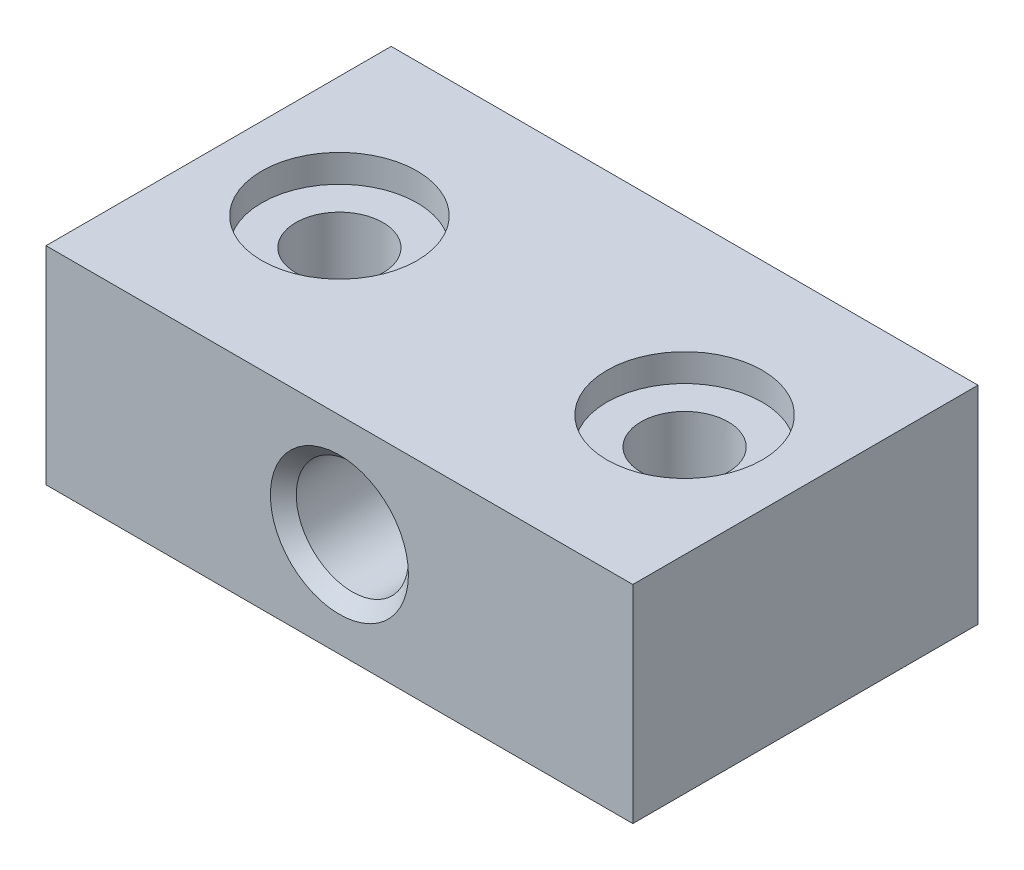
SolidWorks part; units mm, degrees
ref_plane "Front Plane" through (0, 0, 0) normal (0, 0, 1) x (1, 0, 0)
ref_plane "Top Plane" through (0, 0, 0) normal (0, 1, 0) x (1, 0, 0)
ref_plane "Right Plane" through (0, 0, 0) normal (1, 0, 0) x (0, 0, -1)
sketch "Sketch1" plane through (0, 0, 0) normal (0, 0, 1) x (1, 0, 0)
  line L1 (-17, 6) -> (17, 6)
  line L2 (-17, 6) -> (-17, -6)
  line L3 (-17, -6) -> (17, -6)
  line L4 (17, 6) -> (17, -6)
  line L5 (-17, 6) -> (17, -6) construction
  line L6 (-17, -6) -> (17, 6) construction
  point P0 (0, 0)
  dimension "D1" = 34
  dimension "D2" = 12
extrude "Boss-Extrude1" add sketch "Sketch1" against normal blind 20
sketch "Sketch2" plane through (0, 0, 0) normal (0, 0, 1) x (1, 0, 0)
  circle A0 centre (0, 0) radius 3.25
  dimension "D1" = 6.5
extrude "Cut-Extrude1" cut sketch "Sketch2" against normal blind 20 contours A0
sketch "Sketch3" plane through (0, 6, 0) normal (0, 1, 0) x (1, 0, 0)
  line L0 (-17, 20) -> (-17, 0) construction
  line L1 (17, 20) -> (17, 0) construction
  circle A0 centre (-10, 10) radius 2.525
  circle A1 centre (10, 10) radius 2.525
  point P6 (-17, 10)
  point P7 (17, 10)
  dimension "D1" = 5.05
  dimension "D2" = 7
  dimension "D3" = 20
extrude "Cut-Extrude2" cut sketch "Sketch3" against normal blind 20
sketch "Sketch4" plane through (0, 6, 0) normal (0, 1, 0) x (1, 0, 0)
  circle A9 centre (-10, 10) radius 4.5
  circle A10 centre (-10, 10) radius 4.5
  circle A12 centre (10, 10) radius 4.5
  circle A13 centre (10, 10) radius 4.5
  dimension "D1" = 1.975
  dimension "D2" = 1.975
extrude "Cut-Extrude3" cut sketch "Sketch4" against normal blind 1.6
sketch "Sketch5" plane through (0, -6, 0) normal (0, -1, 0) x (1, 0, 0)
  line L1 (10, -5.38) -> (5.999, -7.69)
  line L2 (5.999, -7.69) -> (5.999, -12.31)
  line L3 (5.999, -12.31) -> (10, -14.62)
  line L4 (10, -14.62) -> (14.001, -12.31)
  line L5 (14.001, -12.31) -> (14.001, -7.69)
  line L6 (14.001, -7.69) -> (10, -5.38)
  line L7 (-10, -5.38) -> (-14.001, -7.69)
  line L8 (-14.001, -7.69) -> (-14.001, -12.31)
  line L9 (-14.001, -12.31) -> (-10, -14.62)
  line L10 (-10, -14.62) -> (-5.999, -12.31)
  line L11 (-5.999, -12.31) -> (-5.999, -7.69)
  line L12 (-5.999, -7.69) -> (-10, -5.38)
  circle A0 centre (10, -10) radius 4.001 construction
  circle A1 centre (-10, -10) radius 4.001 construction
  dimension "D1" = 9.24
extrude "Cut-Extrude4" cut sketch "Sketch5" against normal blind 4.97
ref_plane "Plane1" through (0, 0, -22) normal (0, 0, -1) x (-1, 0, 0)
sketch "Sketch6" plane through (0, 0, -22) normal (0, 0, -1) x (-1, 0, 0)
  circle A0 centre (0, 0) radius 3.25 construction
  circle A1 centre (0, 0) radius 3.25
curve "Helix/Spiral1" pitch 8 height 24 turns 3
chamfer "Chamfer1" distance 0.75 angle 45 1 edges at (3.25, 0, -20)
chamfer "Chamfer2" distance 0.75 angle 45 1 edges at (3.25, 0, 0)
sketch "Sketch7" plane through (0, 0, -22) normal (0, 0, -1) x (-1, 0, 0)
  line L0 (3.2839, 0) -> (-3.2161, 0) construction
  line L2 (4.4, 0.9) -> (4.4, -0.9)
  line L3 (-0.8243, 4.3661) -> (0.9757, 4.3661)
  line L4 (0.9757, 4.3661) -> (0.5839, 3.2161)
  line L5 (-0.8243, 4.3661) -> (-0.5161, 3.2161)
  line L6 (-0.5161, 3.2161) -> (-0.5161, -3.2161) construction
  line L7 (0.5839, 3.2161) -> (0.5839, -3.2161) construction
  line L8 (-3.1823, 0.55) -> (3.25, 0.55) construction
  line L9 (-3.1823, -0.55) -> (3.25, -0.55) construction
  line L10 (3.25, 0.55) -> (4.4, 0.9)
  line L11 (3.25, -0.55) -> (4.4, -0.9)
  line L12 (-0.8661, -4.3661) -> (0.9339, -4.3661)
  line L13 (0.5839, -3.2161) -> (0.9339, -4.3661)
  line L14 (-0.5161, -3.2161) -> (-0.8661, -4.3661)
  line L15 (-4.3323, 0.9) -> (-4.3323, -0.9)
  line L16 (-4.3323, -0.9) -> (-3.1823, -0.55)
  line L17 (-3.1823, 0.55) -> (-4.3323, 0.9)
  line L18 (3.25, 0.55) -> (3.25, -0.55) construction
  arc A1 (3.25, 0.55) -> (0.5839, 3.2161) centre (0.0339, 0) ccw
  arc A2 (-0.5161, 3.2161) -> (-3.1823, 0.55) centre (0.0339, 0) ccw
  arc A4 (0.5839, -3.2161) -> (3.25, -0.55) centre (0.0339, 0) ccw
  arc A5 (-3.1823, -0.55) -> (-0.5161, -3.2161) centre (0.0339, 0) ccw
  point P14 (4.4, 0)
  point P30 (-4.3323, 0)
  point P31 (3.25, 0)
  dimension "D5" = 1.1
  dimension "D2" = 1.8
  dimension "D3" = 1.1
  dimension "D4" = 75
  dimension "D6" = 1.15
  dimension "D7" = 1.8
  dimension "D8" = 1.15
  dimension "D9" = 1.8
  dimension "D10" = 1.8
  dimension "D11" = 1.15
  dimension "D13" = 1.15
sketch "Sketch8" plane through (0, 0, -22) normal (0, 0, -1) x (-1, 0, 0)
  line L0 (-4.042, 0.0197) -> (3.958, -0.0019) construction
  line L1 (3.2941, -1.2804) -> (3.2941, 1.2511) construction
  arc A0 (-2.545, -1.3432) -> (-1.4313, -2.4688) centre (-0.042, 0.0197) ccw
  arc A1 (-1.0789, -3.8436) -> (1.0938, -3.8795) centre (0.0711, -0.0125) ccw
  arc A2 (1.4039, -2.5741) -> (2.5491, -1.4408) centre (0.017, -0.0272) ccw
  arc A3 (3.8099, -1.0589) -> (3.8213, 1.0566) centre (-0.042, 0.0197) ccw
  arc A4 (2.461, 1.3826) -> (1.3473, 2.5081) centre (-0.042, 0.0197) ccw
  arc A5 (0.9949, 3.8829) -> (-1.0789, 3.8829) centre (-0.042, 0.0197) ccw
  arc A6 (-1.4049, 2.5227) -> (-2.5411, 1.3898) centre (-0.042, 0.0197) ccw
  arc A7 (-3.9053, 1.0566) -> (-3.9053, -1.0172) centre (-0.042, 0.0197) ccw
  spline S0 degree 3 poles (-1.4313, -2.4688) (-1.4113, -2.9456) (-1.2866, -3.4141) (-1.0789, -3.8436) knots 0 0 0 0 1 1 1 1
  spline S1 degree 3 poles (1.0938, -3.8795) (1.2765, -3.4682) (1.3857, -3.0244) (1.4039, -2.5741) knots 0 0 0 0 1 1 1 1
  spline S2 degree 3 poles (2.5491, -1.4408) (2.9898, -1.3987) (3.4186, -1.2648) (3.8099, -1.0589) knots 0 0 0 0 1 1 1 1
  spline S3 degree 3 poles (3.8213, 1.0566) (3.3938, 1.2521) (2.9309, 1.3672) (2.461, 1.3826) knots 0 0 0 0 1 1 1 1
  spline S4 degree 3 poles (1.3473, 2.5081) (1.3273, 2.985) (1.2026, 3.4534) (0.9949, 3.8829) knots 0 0 0 0 1 1 1 1
  spline S5 degree 3 poles (-1.0789, 3.8829) (-1.2744, 3.4555) (-1.3895, 2.9925) (-1.4049, 2.5227) knots 0 0 0 0 1 1 1 1
  spline S6 degree 3 poles (-2.5411, 1.3898) (-3.0128, 1.3731) (-3.4772, 1.2554) (-3.9053, 1.0566) knots 0 0 0 0 1 1 1 1
  spline S7 degree 3 poles (-3.9053, -1.0172) (-3.4778, -1.2127) (-3.0149, -1.3279) (-2.545, -1.3432) knots 0 0 0 0 1 1 1 1
  point P28 (3.25, 0)
sweep "Cut-Sweep1" [suppressed] cut profiles "Sketch8" path "Helix/Spiral1"
